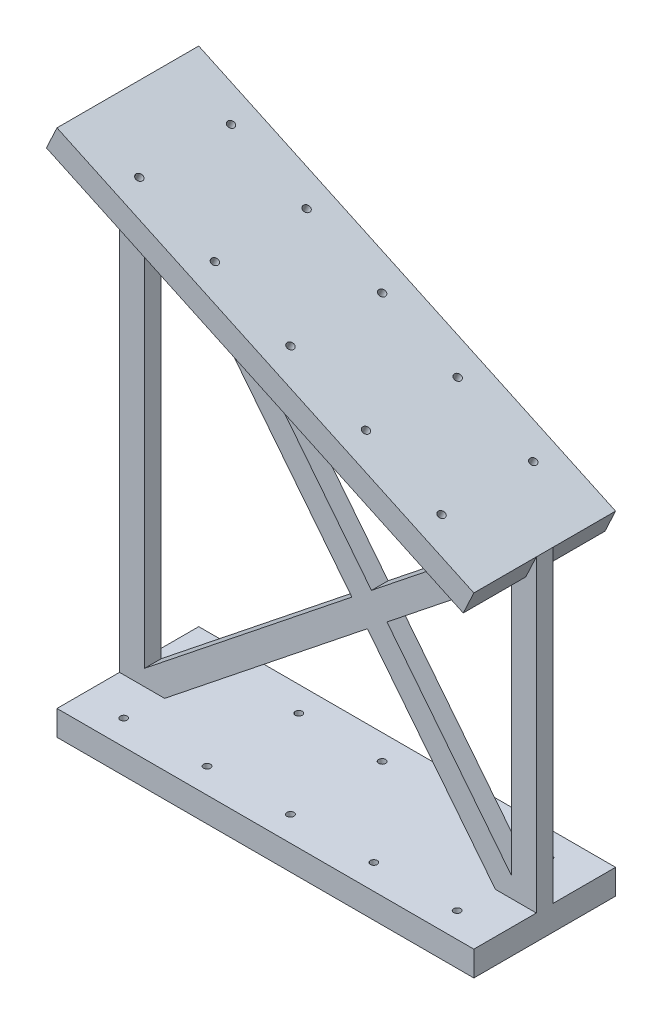
SolidWorks part; units mm, degrees
ref_plane "前视基准面" through (0, 0, 0) normal (0, 0, 1) x (1, 0, 0)
ref_plane "上视基准面" through (0, 0, 0) normal (0, 1, 0) x (1, 0, 0)
ref_plane "右视基准面" through (0, 0, 0) normal (1, 0, 0) x (0, 0, -1)
sketch "草图1" plane through (0, 0, 0) normal (0, 0, 1) x (1, 0, 0)
  line L0 (124.6867, 0) -> (-125.3133, 0)
  line L1 (124.6867, 0) -> (124.6867, 200)
  line L2 (124.6867, 200) -> (-125.3741, 316.6053)
  line L3 (-125.3133, 0) -> (-125.3133, 316.5769)
  line L4 (100.1228, 15) -> (-98.2842, 15)
  line L5 (109.6867, 27.0867) -> (109.6867, 180.8511)
  line L6 (102.0961, 193.9835) -> (-95.157, 285.9641)
  line L7 (-110.3133, 280.9449) -> (-110.3133, 24.5929)
  line L10 (109.6867, 180.8511) -> (35.0892, 121.3616)
  line L11 (100.1228, 15) -> (23.3616, 112.0092)
  line L12 (100.3344, 192.5786) -> (25.7814, 133.1246)
  line L13 (109.6867, 27.0867) -> (35.0892, 121.3616)
  line L14 (100.3344, 192.5786) -> (102.0961, 193.9835)
  line L15 (-107.6365, 26.7275) -> (-110.3133, 24.5929)
  line L16 (25.7814, 133.1246) -> (-95.157, 285.9641)
  line L17 (14.0538, 123.7722) -> (-110.3133, 280.9449)
  line L18 (14.0538, 123.7722) -> (-107.6365, 26.7275)
  line L19 (23.3616, 112.0092) -> (-98.2842, 15)
  point P10 (-0.3437, 258.3026)
  dimension "D1" = 250
  dimension "D2" = 200
  dimension "D3" = 25
  dimension "D4" = 124.6867
  dimension "D5" = 15
  dimension "D6" = 15
  dimension "D7" = 15
  dimension "D8" = 15
  dimension "D9" = 38.571
  dimension "D10" = 155.5908
  dimension "D11" = 15
  dimension "D12" = 89.782
  dimension "D13" = 15
  dimension "D14" = 200.4256
extrude "凸台-拉伸1" add sketch "草图1" along normal blind 10 contours L3 L0 L1 L2 L19 L11 L4 L5 L13 L10 L12 L16 L6 L14 L17 L18 L15 L7 region at (-0.3133, 4.0339, 0)
sketch "草图3" plane through (0, 0, 0) normal (0, -1, 0) x (1, 0, 0)
  line L0 (-132.5956, 5) -> (137.3749, 5) construction
  line L1 (-0.3133, -3.4989) -> (-0.3133, 12.7515) construction
  line L3 (-125.3133, 17.5) -> (124.6867, 17.5)
  line L4 (124.6867, 17.5) -> (124.6867, -7.5)
  line L5 (124.6867, -7.5) -> (-125.3133, -7.5)
  line L7 (-125.3133, 17.5) -> (-125.3133, -7.5)
  dimension "D1" = 12.5
  dimension "D2" = 12.5
extrude "凸台-拉伸3" add sketch "草图3" against normal blind 15
sketch "草图4" plane through (98.8743, 212.0365, 0) normal (0.4226, 0.9063, 0) x (0.9063, -0.4226, 0)
  line L0 (-265.2486, -5) -> (43.6588, -5) construction
  line L1 (-110.7949, 37.6957) -> (-110.7949, -42.1651) construction
  line L2 (-247.3636, -17.5) -> (-247.3636, 7.5)
  line L3 (-247.3636, 7.5) -> (28.4809, 7.5)
  line L4 (28.4809, 7.5) -> (28.4809, -17.5)
  line L5 (-247.3636, -17.5) -> (28.4809, -17.5)
  dimension "D1" = 12.5
  dimension "D2" = 12.5
extrude "凸台-拉伸4" add sketch "草图4" against normal blind 15
sketch "草图10" plane through (0, 0, 0) normal (0, -1, 0) x (1, 0, 0)
  line L0 (-155.3133, 47.5) -> (-155.3133, -37.5) construction
  line L1 (-155.3133, -37.5) -> (154.6867, -37.5) construction
  line L2 (154.6867, -37.5) -> (154.6867, 47.5) construction
  line L3 (154.6867, 47.5) -> (-155.3133, 47.5) construction
  line L4 (-125.3133, 17.5) -> (-125.3133, -7.5)
  line L5 (-125.3133, -7.5) -> (124.6867, -7.5)
  line L6 (124.6867, -7.5) -> (124.6867, 17.5)
  line L7 (124.6867, 17.5) -> (-125.3133, 17.5)
  line L8 (-125.3133, 17.5) -> (-125.3133, -7.5) construction
  line L9 (-125.3133, -7.5) -> (124.6867, -7.5) construction
  line L10 (124.6867, -7.5) -> (124.6867, 17.5) construction
  line L11 (124.6867, 17.5) -> (-125.3133, 17.5) construction
  line L12 (-125.3133, 17.5) -> (124.6867, 17.5)
  line L13 (-125.3133, -7.5) -> (124.6867, -7.5)
  line L14 (124.6867, -7.5) -> (124.6867, -37.5)
  line L15 (124.6867, -37.5) -> (-125.3133, -37.5)
  line L16 (-125.3133, -37.5) -> (-125.3133, -7.5)
  line L17 (-125.3133, 17.5) -> (-125.3133, 47.5)
  line L18 (-125.3133, 47.5) -> (124.6867, 47.5)
  line L19 (124.6867, 47.5) -> (124.6867, 17.5)
  dimension "D1" = 0
  dimension "D2" = 30
extrude "凸台-拉伸5" add sketch "草图10" against normal up to surface (15 mm away) up to face at (0.0976, 15, 5)
sketch "草图11" plane through (98.8743, 212.0365, 0) normal (0.4226, 0.9063, 0) x (0.9063, -0.4226, 0)
  line L0 (58.4809, -10) -> (58.4809, 0) construction
  line L1 (58.4809, 0) -> (58.4809, 37.5) construction
  line L2 (58.4809, 37.5) -> (-277.3636, 37.5) construction
  line L3 (-277.3636, 37.5) -> (-277.3636, -47.5) construction
  line L4 (-277.3636, -47.5) -> (58.4809, -47.5) construction
  line L5 (58.4809, -47.5) -> (58.4809, -10) construction
  line L6 (28.4809, -10) -> (28.4809, 0)
  line L7 (28.4809, 0) -> (28.4809, 7.5)
  line L8 (28.4809, 7.5) -> (-247.3636, 7.5)
  line L9 (-247.3636, 7.5) -> (-247.3636, -17.5)
  line L10 (-247.3636, -17.5) -> (28.4809, -17.5)
  line L11 (28.4809, -17.5) -> (28.4809, -10)
  line L12 (28.4809, -10) -> (28.4809, 0) construction
  line L13 (28.4809, 0) -> (28.4809, 7.5) construction
  line L14 (28.4809, 7.5) -> (-247.3636, 7.5) construction
  line L15 (-247.3636, 7.5) -> (-247.3636, -17.5) construction
  line L16 (-247.3636, -17.5) -> (28.4809, -17.5) construction
  line L17 (28.4809, -17.5) -> (28.4809, -10) construction
  line L18 (-247.3636, 7.5) -> (-247.3636, 37.5)
  line L19 (-247.3636, 37.5) -> (28.4809, 37.5)
  line L20 (28.4809, 37.5) -> (28.4809, 7.5)
  line L21 (28.4809, 7.5) -> (-247.3636, 7.5)
  line L22 (-247.3636, -17.5) -> (-247.3636, -47.5)
  line L23 (-247.3636, -47.5) -> (28.4809, -47.5)
  line L24 (28.4809, -47.5) -> (28.4809, -17.5)
  line L25 (28.4809, -17.5) -> (-247.3636, -17.5)
  dimension "D1" = 0
  dimension "D2" = 30
extrude "凸台-拉伸6" add sketch "草图11" against normal up to surface (15 mm away) up to face at (-110.2351, 292.9952, 5)
sketch "草图13" plane through (0, 0, 0) normal (0, -1, 0) x (1, 0, 0)
  line L0 (-125.3133, 47.5) -> (-125.3133, -37.5) construction
  line L1 (-125.3133, 47.5) -> (-125.3133, -37.5) construction
  line L2 (-174.9694, 5) -> (145.3231, 5) construction
  line L4 (-112.8133, 32) -> (112.1867, 32)
  line L5 (-0.3133, 101.392) -> (-0.3133, -89.1793) construction
  line L6 (-112.8133, 32) -> (-112.8133, 5)
  line L7 (-112.8133, 5) -> (112.1867, 5)
  line L8 (112.1867, 5) -> (112.1867, 32)
  circle A0 centre (-100.3133, 32.5) radius 2.5
  point P10 (-0.3133, 32)
  dimension "D3" = 5
  dimension "D1" = 27
  dimension "D2" = 112.5
  dimension "D4" = 27.5
  dimension "D5" = 12.5
sketch "草图15" plane through (0, 15, 0) normal (0, 1, 0) x (1, 0, 0)
  circle A0 centre (-100.3133, -32.5) radius 2.5 construction
  circle A1 centre (-100.3133, -32.5) radius 2.5
hole_wizard "M5 螺纹孔1" positions "3D草图2" profile "草图17" tap size "M5" standard "GB" end condition through all
sketch3d "3D草图2"
  point P0 (-100.3133, 15, 32.5)
sketch "草图17" plane through (-100.3133, 15, 32.5) normal (1, 0, 0) x (0, 0, 1)
  line L0 (0, 0) -> (0, 15)
  line L1 (0, 15) -> (2.1, 15)
  line L2 (2.1, 15) -> (2.1, 0)
  line L5 (2.1, 0) -> (0, 0)
  line L11 (0, -6.35) -> (0, 107.95) construction
  dimension "通孔螺纹孔钻头直径" = 4.2
  dimension "通孔螺纹孔钻头深度" = 15
pattern_linear "阵列(线性)1" count 5 spacing 50 along (1, 0, 0) of "M5 螺纹孔1"
ref_plane "基准面1" through (0, 0, 5) normal (0, 0, -1) x (-1, 0, 0)
mirror "镜向1" about plane through (0, 0, 5) normal (0, 0, -1) of "阵列(线性)1", "M5 螺纹孔1"
sketch "草图18" plane through (98.8743, 212.0365, 0) normal (0.4226, 0.9063, 0) x (0.9063, -0.4226, 0)
  line L0 (28.4809, 37.5) -> (-247.3636, 37.5) construction
  line L1 (-247.3636, -47.5) -> (-247.3636, 37.5) construction
  line L2 (28.4809, 37.5) -> (-247.3636, 37.5) construction
  line L3 (-247.3636, -47.5) -> (-247.3636, 37.5) construction
  line L4 (-281.3225, -5) -> (59.4867, -5) construction
  line L5 (-109.4413, 95.8431) -> (-109.4413, -96.4665) construction
  line L6 (-221.9413, 22) -> (-109.4413, 22)
  line L7 (-221.9413, 22) -> (-221.9413, -5)
  circle A0 centre (-209.4413, 22.5) radius 2.5
  circle A1 centre (-159.4413, 22.5) radius 2.5
  circle A2 centre (-109.4413, 22.5) radius 2.5
  circle A3 centre (-59.4413, 22.5) radius 2.5
  circle A4 centre (-9.4413, 22.5) radius 2.5
  circle A5 centre (-9.4413, -32.5) radius 2.5
  circle A6 centre (-59.4413, -32.5) radius 2.5
  circle A7 centre (-109.4413, -32.5) radius 2.5
  circle A8 centre (-159.4413, -32.5) radius 2.5
  circle A9 centre (-209.4413, -32.5) radius 2.5
  dimension "D3" = 5
  dimension "D1" = 112.5
  dimension "D2" = 27
  dimension "D4" = 12.5
  dimension "D5" = 27.5
  dimension "D6" = 5
hole_wizard "M5 螺纹孔2" positions "3D草图3" profile "草图19" tap size "M5" standard "GB" end condition up to next
sketch3d "3D草图3"
  point P0 (-90.9441, 300.5503, -22.5)
sketch "草图19" plane through (-90.9441, 300.5503, -22.5) normal (0, 0, 1) x (-0.9063, 0.4226, 0)
  line L0 (0, 0) -> (0, 15)
  line L1 (0, 15) -> (2.1, 15)
  line L2 (2.1, 15) -> (2.1, 0)
  line L5 (2.1, 0) -> (0, 0)
  line L11 (0, -6.35) -> (0, 107.95) construction
  dimension "通孔螺纹孔钻头直径" = 4.2
  dimension "通孔螺纹孔钻头深度" = 15
pattern_linear "阵列(线性)2" count 5 spacing 50 along (0.9063, -0.4226, 0) of "M5 螺纹孔2"
hole_wizard "M5 螺纹孔3" positions "3D草图4" profile "草图20" tap size "M5" standard "GB" end condition up to next
sketch3d "3D草图4"
  point P0 (-90.9441, 300.5503, 32.5)
sketch "草图20" plane through (-90.9441, 300.5503, 32.5) normal (0, 0, 1) x (-0.9063, 0.4226, 0)
  line L0 (0, 0) -> (0, 15)
  line L1 (0, 15) -> (2.1, 15)
  line L2 (2.1, 15) -> (2.1, 0)
  line L5 (2.1, 0) -> (0, 0)
  line L11 (0, -6.35) -> (0, 107.95) construction
  dimension "通孔螺纹孔钻头直径" = 4.2
  dimension "通孔螺纹孔钻头深度" = 15
pattern_linear "阵列(线性)3" count 5 spacing 50 along (0.9063, -0.4226, 0) of "M5 螺纹孔3"
